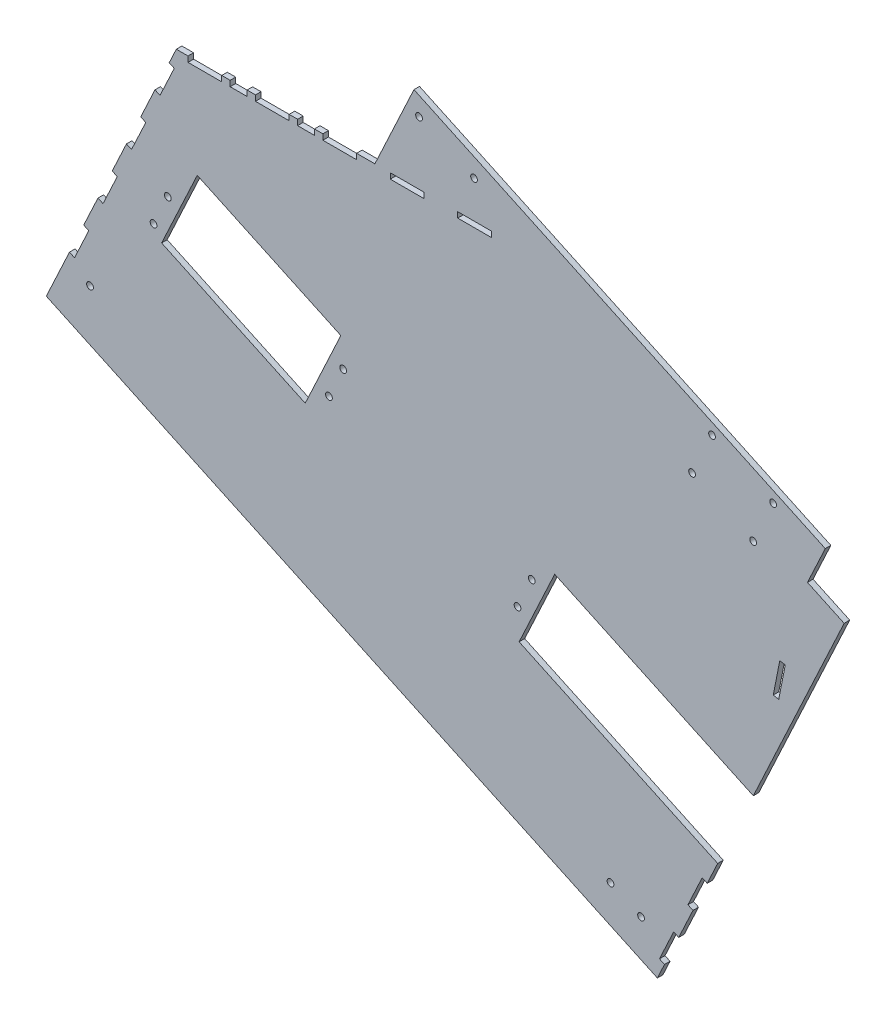
SolidWorks part; units mm, degrees
material "Balsa"
ref_plane "Front Plane" through (0, 0, 0) normal (0, 0, 1) x (1, 0, 0)
ref_plane "Top Plane" through (0, 0, 0) normal (0, 1, 0) x (1, 0, 0)
ref_plane "Right Plane" through (0, 0, 0) normal (1, 0, 0) x (0, 0, -1)
sketch "Sketch1" plane through (0, 0, 0) normal (0, 0, 1) x (1, 0, 0)
  line L0 (-255.2098, 12.6381) -> (-137.4275, 12.6381)
  line L1 (-137.4275, 12.6381) -> (-114.243, 62.3574)
  line L2 (-114.243, 62.3574) -> (129.7831, -51.4338)
  line L3 (129.7831, -51.4338) -> (119.2177, -74.0915)
  line L4 (119.2177, -74.0915) -> (140.969, -84.2344)
  line L5 (140.969, -84.2344) -> (30.1585, -321.8683)
  line L6 (30.1585, -321.8683) -> (-332.3646, -152.8209)
  line L7 (-332.3646, -152.8209) -> (-255.2098, 12.6381)
  line L9 (-332.3646, -152.8209) -> (-261.0998, 0.0069) construction
  line L10 (30.1585, -321.8683) -> (-332.3646, -152.8209) construction
  line L11 (140.969, -84.2344) -> (30.1585, -321.8683) construction
  line L12 (-189.2372, 97.3278) -> (129.7831, -51.4338) construction
  line L13 (119.2177, -74.0915) -> (140.969, -84.2344) construction
  line L14 (129.7831, -51.4338) -> (119.2177, -74.0915) construction
  circle A0 centre (87.0035, -69.0002) radius 2
  circle A1 centre (98.8369, -43.6236) radius 2
  circle A2 centre (62.5845, -26.7189) radius 2
  circle A3 centre (50.7512, -52.0955) radius 2
  circle A4 centre (2.3586, -286.8374) radius 2
  circle A5 centre (-306.4229, -134.5749) radius 2
  circle A6 centre (20.4847, -295.2897) radius 2
  circle A7 centre (2.3586, -286.8374) radius 2 construction
  circle A8 centre (20.4847, -295.2897) radius 2 construction
  dimension "D1" = 4
  dimension "D2" = 4
  dimension "D3" = 4
  dimension "D4" = 4
  dimension "D7" = 4
  dimension "D5" = 27.5
  dimension "D6" = 15.8
extrude "Boss-Extrude1" add sketch "Sketch1" along normal up to surface (3.3 mm away)
sketch "Sketch2" plane through (0, 0, 0) normal (0, 0, -1) x (-1, 0, 0)
  line L0 (114.243, 62.3574) -> (137.4275, 12.6381) construction
  line L1 (-129.7831, -51.4338) -> (114.243, 62.3574) construction
  circle A0 centre (78.5916, 34.6991) radius 2
  circle A1 centre (111.2187, 49.9134) radius 2
  dimension "D1" = 4
  dimension "D2" = 4
  dimension "D3" = 8
  dimension "D4" = 36
  dimension "D5" = 10
  dimension "D6" = 10
extrude "Cut-Extrude1" cut sketch "Sketch2" against normal through all
sketch "Sketch5" plane through (0, 0, 3.3) normal (0, 0, 1) x (1, 0, 0)
  line L0 (65.9543, -245.104) -> (-51.8657, -190.1636)
  line L1 (140.969, -84.2344) -> (30.1585, -321.8683) construction
  line L2 (-51.8657, -190.1636) -> (-30.7348, -144.8482)
  line L3 (-30.7348, -144.8482) -> (87.0852, -199.7886)
  line L4 (87.0852, -199.7886) -> (65.9543, -245.104)
  line L5 (119.2177, -74.0915) -> (140.969, -84.2344) construction
  dimension "D1" = 130
  dimension "D2" = 127.5
  dimension "D3" = 50
extrude "Cut-Extrude2" cut sketch "Sketch5" against normal blind 10
sketch "Sketch6" plane through (0, 0, 3.3) normal (0, 0, 1) x (1, 0, 0)
  line L0 (-178.7488, -130.9971) -> (-157.6179, -85.6817)
  line L1 (-157.6179, -85.6817) -> (-242.8108, -45.9555)
  line L2 (-242.8108, -45.9555) -> (-263.9417, -91.2709)
  line L3 (-263.9417, -91.2709) -> (-178.7488, -130.9971)
  line L5 (87.0852, -199.7886) -> (-30.7348, -144.8482) construction
  line L6 (-51.8657, -190.1636) -> (65.9543, -245.104) construction
  line L7 (-332.3646, -152.8209) -> (-255.2098, 12.6381) construction
  line L8 (129.7831, -51.4338) -> (119.2177, -74.0915) construction
  dimension "D1" = 130
  dimension "D2" = 340
extrude "Cut-Extrude3" cut sketch "Sketch6" against normal blind 10
sketch "Sketch7" plane through (0, 0, 3.3) normal (0, 0, 1) x (1, 0, 0)
  circle A0 centre (-52.7985, -172.5711) radius 2
  circle A1 centre (-44.3462, -154.4449) radius 2
  circle A2 centre (-164.6725, -120.4034) radius 2
  circle A3 centre (-156.2202, -102.2772) radius 2
  circle A4 centre (-52.7985, -172.5711) radius 2 construction
  circle A5 centre (-44.3462, -154.4449) radius 2 construction
  circle A6 centre (-164.6725, -120.4034) radius 2 construction
  circle A7 centre (-156.2202, -102.2772) radius 2 construction
extrude "Cut-Extrude4" cut sketch "Sketch7" against normal blind 10
sketch "Sketch8" plane through (0, 0, 3.3) normal (0, 0, 1) x (1, 0, 0)
  line L0 (-255.2098, 12.6381) -> (-137.4275, 12.6381) construction
  line L1 (-248.2814, 12.6381) -> (-228.2814, 12.6381)
  line L2 (-248.2814, 12.6381) -> (-248.2814, 9.3381)
  line L3 (-248.2814, 9.3381) -> (-228.2814, 9.3381)
  line L4 (-228.2814, 12.6381) -> (-228.2814, 9.3381)
  line L5 (-248.2814, 12.6381) -> (-228.2814, 9.3381) construction
  line L6 (-248.2814, 9.3381) -> (-228.2814, 12.6381) construction
  line L7 (-248.2814, 9.3381) -> (-248.2814, 12.6381) construction
  line L8 (-208.2814, 12.6381) -> (-188.2814, 12.6381)
  line L9 (-208.2814, 12.6381) -> (-208.2814, 9.3381)
  line L10 (-208.2814, 9.3381) -> (-188.2814, 9.3381)
  line L11 (-188.2814, 12.6381) -> (-188.2814, 9.3381)
  line L12 (-208.2814, 12.6381) -> (-188.2814, 9.3381) construction
  line L13 (-208.2814, 9.3381) -> (-188.2814, 12.6381) construction
  line L14 (-168.2814, 12.6381) -> (-148.2814, 12.6381)
  line L15 (-168.2814, 12.6381) -> (-168.2814, 9.3381)
  line L16 (-168.2814, 9.3381) -> (-148.2814, 9.3381)
  line L17 (-148.2814, 12.6381) -> (-148.2814, 9.3381)
  line L18 (-168.2814, 12.6381) -> (-148.2814, 9.3381) construction
  line L19 (-168.2814, 9.3381) -> (-148.2814, 12.6381) construction
  line L20 (-128.2814, 12.6381) -> (-108.2814, 12.6381)
  line L21 (-128.2814, 12.6381) -> (-128.2814, 9.3381)
  line L22 (-128.2814, 9.3381) -> (-108.2814, 9.3381)
  line L23 (-108.2814, 12.6381) -> (-108.2814, 9.3381)
  line L24 (-128.2814, 12.6381) -> (-108.2814, 9.3381) construction
  line L25 (-128.2814, 9.3381) -> (-108.2814, 12.6381) construction
  line L26 (-88.2814, 12.6381) -> (-68.2814, 12.6381)
  line L27 (-88.2814, 12.6381) -> (-88.2814, 9.3381)
  line L28 (-88.2814, 9.3381) -> (-68.2814, 9.3381)
  line L29 (-68.2814, 12.6381) -> (-68.2814, 9.3381)
  line L30 (-88.2814, 12.6381) -> (-68.2814, 9.3381) construction
  line L31 (-88.2814, 9.3381) -> (-68.2814, 12.6381) construction
  point P4 (-238.2814, 10.9881)
  point P14 (-198.2814, 10.9881)
  point P19 (-158.2814, 10.9881)
  point P24 (-118.2814, 10.9881)
  point P30 (-78.2814, 10.9881)
  dimension "D1" = 20
  dimension "D2" = 3.3
  dimension "D3" = 5
extrude "Cut-Extrude5" cut sketch "Sketch8" against normal blind 10
sketch "Sketch9" plane through (0, 0, 3.3) normal (0, 0, 1) x (1, 0, 0)
  line L0 (-259.4359, 3.575) -> (-256.4451, 2.1804)
  line L1 (-332.3646, -152.8209) -> (-255.2098, 12.6381) construction
  line L2 (-256.4451, 2.1804) -> (-264.8975, -15.9458)
  line L3 (-264.8975, -15.9458) -> (-267.8883, -14.5511)
  line L4 (-267.8883, -14.5511) -> (-259.4359, 3.575)
  line L5 (-276.3407, -32.6773) -> (-273.3499, -34.0719)
  line L6 (-273.3499, -34.0719) -> (-281.8022, -52.1981)
  line L7 (-281.8022, -52.1981) -> (-284.793, -50.8035)
  line L8 (-284.793, -50.8035) -> (-276.3407, -32.6773)
  line L9 (-293.2454, -68.9296) -> (-290.2546, -70.3242)
  line L10 (-290.2546, -70.3242) -> (-298.707, -88.4504)
  line L11 (-298.707, -88.4504) -> (-301.6978, -87.0558)
  line L12 (-301.6978, -87.0558) -> (-293.2454, -68.9296)
  line L13 (-310.1501, -105.1819) -> (-307.1593, -106.5766)
  line L14 (-307.1593, -106.5766) -> (-315.6117, -124.7027)
  line L15 (-315.6117, -124.7027) -> (-318.6025, -123.3081)
  line L16 (-318.6025, -123.3081) -> (-310.1501, -105.1819)
  dimension "D1" = 3.3
  dimension "D2" = 20
  dimension "D3" = 10
  dimension "D4" = 4
extrude "Cut-Extrude6" cut sketch "Sketch9" against normal blind 10
sketch "Sketch10" plane through (0, 0, 3.3) normal (0, 0, 1) x (1, 0, 0)
  line L0 (-255.2098, 12.6381) -> (-223.2814, 12.6381) construction
  line L1 (-173.2814, 12.6381) -> (-183.2814, 12.6381)
  line L2 (-173.2814, 12.6381) -> (-173.2814, 9.3381)
  line L3 (-173.2814, 9.3381) -> (-183.2814, 9.3381)
  line L4 (-183.2814, 12.6381) -> (-183.2814, 9.3381)
  line L5 (-173.2814, 12.6381) -> (-183.2814, 9.3381) construction
  line L6 (-173.2814, 9.3381) -> (-183.2814, 12.6381) construction
  line L7 (-188.2814, 9.3381) -> (-188.2814, 12.6381) construction
  line L8 (-213.2814, 12.6381) -> (-223.2814, 12.6381)
  line L9 (-213.2814, 12.6381) -> (-213.2814, 9.3381)
  line L10 (-213.2814, 9.3381) -> (-223.2814, 9.3381)
  line L11 (-223.2814, 12.6381) -> (-223.2814, 9.3381)
  line L12 (-213.2814, 12.6381) -> (-223.2814, 9.3381) construction
  line L13 (-213.2814, 9.3381) -> (-223.2814, 12.6381) construction
  point P4 (-178.2814, 10.9881)
  point P15 (-218.2814, 10.9881)
  dimension "D1" = 10
  dimension "D2" = 3.3
  dimension "D3" = 5
  dimension "D4" = 2
extrude "Cut-Extrude7" cut sketch "Sketch10" against normal blind 3.3
sketch "Sketch11" plane through (0, 0, 3.3) normal (0, 0, 1) x (1, 0, 0)
  line L0 (34.3847, -312.8052) -> (31.3939, -311.4105)
  line L1 (65.9543, -245.104) -> (30.1585, -321.8683) construction
  line L2 (31.3939, -311.4105) -> (39.8463, -293.2844)
  line L3 (39.8463, -293.2844) -> (42.8371, -294.679)
  line L4 (42.8371, -294.679) -> (34.3847, -312.8052)
  line L5 (30.1585, -321.8683) -> (-332.3646, -152.8209) construction
  line L6 (51.2895, -276.5529) -> (48.2986, -275.1582)
  line L7 (48.2986, -275.1582) -> (56.751, -257.0321)
  line L8 (56.751, -257.0321) -> (59.7418, -258.4267)
  line L9 (59.7418, -258.4267) -> (51.2895, -276.5529)
  dimension "D1" = 3.3
  dimension "D2" = 20
  dimension "D3" = 10
  dimension "D4" = 2
extrude "Cut-Extrude8" cut sketch "Sketch11" against normal blind 3.3
sketch "Sketch12" plane through (0, 0, 0) normal (0, 0, -1) x (-1, 0, 0)
  line L0 (-102.7901, -122.4718) -> (-98.923, -142.0944)
  line L1 (-102.7901, -122.4718) -> (-106.0279, -123.1099)
  line L2 (-98.923, -142.0944) -> (-102.1607, -142.7325)
  line L3 (-106.0279, -123.1099) -> (-102.1607, -142.7325)
  line L4 (-119.2177, -74.0915) -> (-140.969, -84.2344) construction
  line L6 (-93.7982, -185.1655) -> (-102.1607, -142.7325) construction
  dimension "D1" = 50
  dimension "D2" = 3.3
  dimension "D3" = 20
extrude "Cut-Extrude9" cut sketch "Sketch12" against normal blind 3.3
sketch "Sketch13" plane through (0, 0, 3.3) normal (0, 0, 1) x (1, 0, 0)
  circle A0 centre (-268.7316, -83.7963) radius 2.0107
  circle A1 centre (-260.2792, -65.6702) radius 2
  circle A2 centre (-268.7316, -83.7963) radius 2.0107 construction
  circle A3 centre (-260.2792, -65.6702) radius 2 construction
extrude "Cut-Extrude10" cut sketch "Sketch13" against normal blind 10
